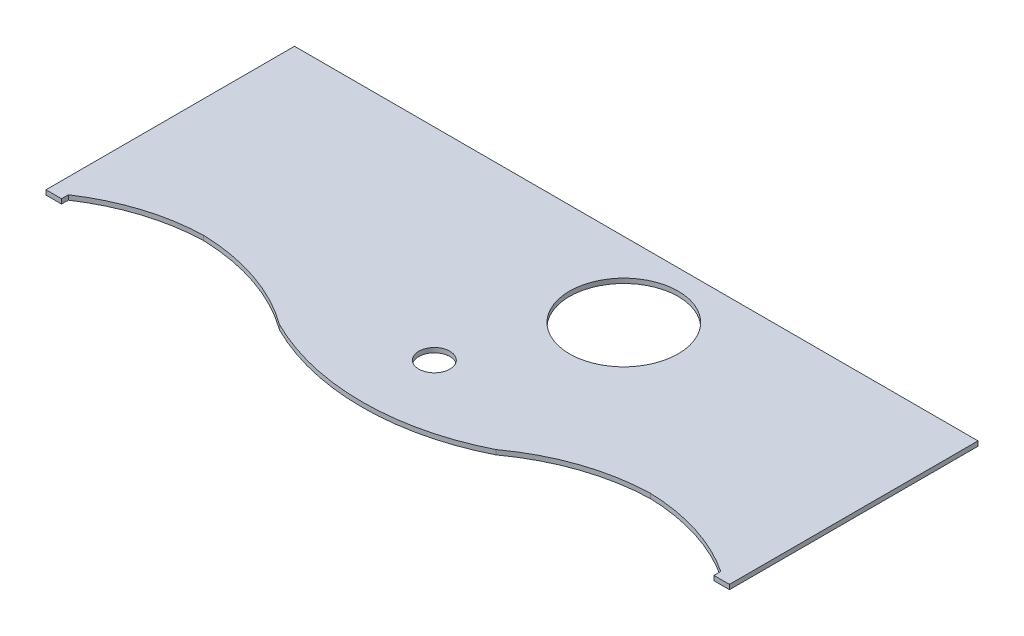
SolidWorks part; units mm, degrees
ref_plane "Front Plane" through (0, 0, 0) normal (0, 0, 1) x (1, 0, 0)
ref_plane "Top Plane" through (0, 0, 0) normal (0, 1, 0) x (1, 0, 0)
ref_plane "Right Plane" through (0, 0, 0) normal (1, 0, 0) x (0, 0, -1)
ref_plane "Plane1" through (0, 4.5, 0) normal (0, 1, 0) x (1, 0, 0)
ref_plane "Plane2" through (0, 3, 0) normal (0, -1, 0) x (-1, 0, 0)
sketch "Sketch1" plane through (0, 3, 0) normal (0, -1, 0) x (-1, 0, 0)
  line L0 (0, -100) -> (0, 70) construction
  line L3 (110, 50) -> (-110, 50)
  line L5 (-34.8399, -30) -> (34.8399, -30) construction
  line L6 (-110, 50) -> (-110, -30)
  line L7 (-110, -30) -> (-105, -30.0025)
  line L8 (-105, -30.0025) -> (-105, -27.799)
  line L9 (110, 50) -> (110, -30)
  line L10 (110, -30) -> (105, -30.0025)
  line L11 (105, -30.0025) -> (105, -27.799)
  arc A0 (-105, -27.799) -> (-71.9147, -17.3273) centre (-70.2175, -80.192) cw
  arc A1 (-71.9147, -17.3273) -> (-105, -27.799) centre (-70.2175, -80.192) ccw construction
  arc A2 (-71.9147, -17.3273) -> (-34.8399, -30) centre (-73.6989, -83.1159) cw
  arc A3 (-34.8399, -30) -> (-71.9147, -17.3273) centre (-73.6989, -83.1159) ccw construction
  arc A4 (-34.8399, -30) -> (34.8399, -30) centre (0, 39.341) ccw
  arc A6 (34.8399, -30) -> (71.9147, -17.3273) centre (73.6989, -83.1159) cw
  arc A7 (71.9147, -17.3273) -> (34.8399, -30) centre (73.6989, -83.1159) ccw construction
  arc A8 (71.9147, -17.3273) -> (105, -27.799) centre (70.2175, -80.192) cw
  arc A9 (105, -27.799) -> (71.9147, -17.3273) centre (70.2175, -80.192) ccw construction
  circle A11 centre (0, -15) radius 5
  circle A12 centre (-20, 26) radius 17.5
  circle A13 centre (-20, 26) radius 17.5 construction
  circle A14 centre (0, -15) radius 5 construction
  arc A15 (-34.8399, -30) -> (34.8399, -30) centre (0, 39.341) ccw construction
extrude "Boss-Extrude1" add sketch "Sketch1" against normal up to surface (1.5 mm away) up to plane "Plane1"
